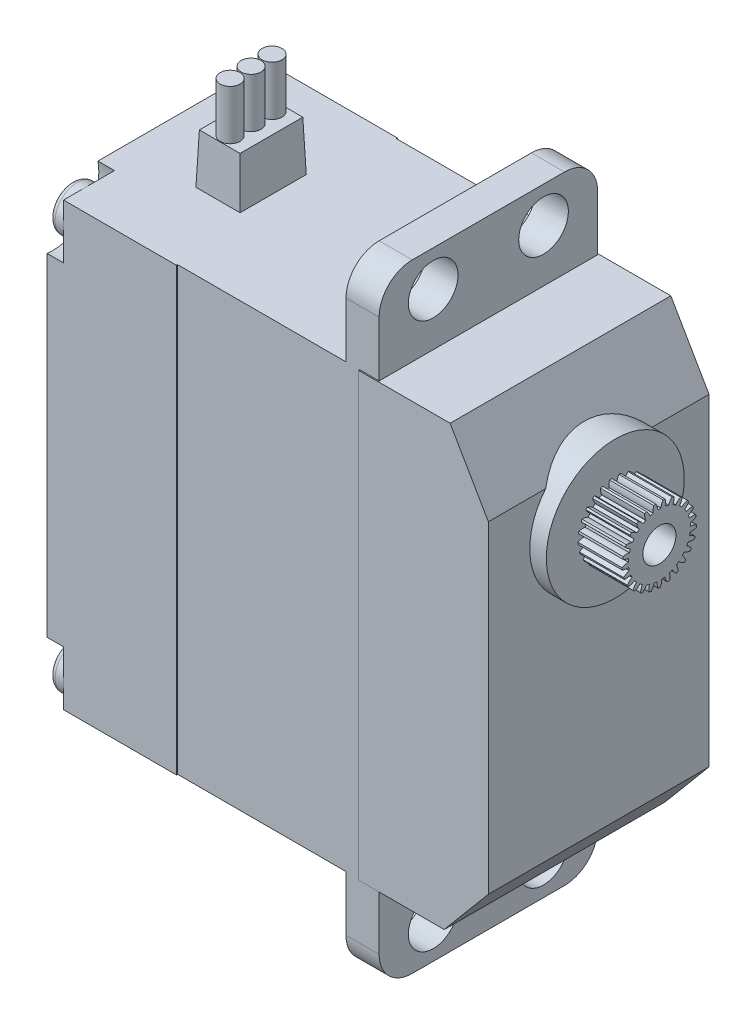
SolidWorks part; units mm, degrees
material "AISI 304"
ref_plane "前视基准面" through (0, 0, 0) normal (0, 0, 1) x (1, 0, 0)
ref_plane "上视基准面" through (0, 0, 0) normal (0, 1, 0) x (1, 0, 0)
ref_plane "右视基准面" through (0, 0, 0) normal (1, 0, 0) x (0, 0, -1)
sketch "草图1" plane through (0, 0, 0) normal (0, 0, 1) x (1, 0, 0)
  line L1 (-20, -20) -> (20, -20)
  line L2 (-20, -20) -> (-20, 20)
  line L3 (-20, 20) -> (20, 20)
  line L4 (20, -20) -> (20, 20)
  line L5 (-20, -20) -> (20, 20) construction
  line L6 (-20, 20) -> (20, -20) construction
  point P0 (0, 0)
  dimension "D1" = 40
  dimension "D2" = 40
extrude "凸台-拉伸1" add sketch "草图1" along normal blind 20
ref_plane "基准面1" through (20, 0, 0) normal (1, 0, 0) x (0, 0, -1)
sketch "草图2" plane through (20, 0, 0) normal (1, 0, 0) x (0, 0, -1)
  line L0 (-10, 20) -> (-10, 10) construction
  line L1 (-20, 20) -> (0, 20) construction
  line L2 (0, -20) -> (0, 20) construction
  line L3 (-20, -20) -> (-20, 20) construction
  circle A0 centre (-10, 10) radius 6.25
  dimension "D2" = 12.5
  dimension "D1" = 10
extrude "凸台-拉伸2" add sketch "草图2" along normal blind 1.5
ref_plane "基准面2" through (-20, 0, 0) normal (-1, 0, 0) x (0, 0, 1)
ref_plane "基准面5" through (20, 0, 0) normal (1, 0, 0) x (0, 0, -1)
ref_plane "基准面8" through (0, 0, 0) normal (0, 0, -1) x (-1, 0, 0)
sketch "草图10" plane through (0, 0, 0) normal (0, 0, -1) x (-1, 0, 0)
  line L0 (-20, 20) -> (20, 20) construction
  line L1 (-8.25, -20) -> (8.25, -20)
  line L2 (-8.25, -20) -> (-8.25, 20)
  line L3 (-8.25, 20) -> (8.25, 20)
  line L4 (8.25, -20) -> (8.25, 20)
  line L5 (-8.25, -20) -> (8.25, 20) construction
  line L6 (-8.25, 20) -> (8.25, -20) construction
  point P0 (0, 0)
  dimension "D1" = 16.5
extrude "切除-拉伸5" cut sketch "草图10" against normal blind 0.1
ref_plane "基准面9" through (0, 0, 20) normal (0, 0, 1) x (1, 0, 0)
sketch "草图11" plane through (0, 0, 20) normal (0, 0, 1) x (1, 0, 0)
  line L0 (20, 20) -> (-20, 20) construction
  line L1 (-8.25, -20) -> (8.25, -20)
  line L2 (-8.25, -20) -> (-8.25, 20)
  line L3 (-8.25, 20) -> (8.25, 20)
  line L4 (8.25, -20) -> (8.25, 20)
  line L5 (-8.25, -20) -> (8.25, 20) construction
  line L6 (-8.25, 20) -> (8.25, -20) construction
  point P0 (0, 0)
  dimension "D1" = 16.5
extrude "切除-拉伸6" cut sketch "草图11" against normal blind 0.1
ref_plane "基准面10" through (0, 20, 0) normal (0, 1, 0) x (1, 0, 0)
ref_plane "基准面11" through (0, -20, 0) normal (0, -1, 0) x (-1, 0, 0)
ref_plane "基准面12" through (21.5, 0, 0) normal (1, 0, 0) x (0, 0, -1)
sketch "草图14" plane through (21.5, 0, 0) normal (1, 0, 0) x (0, 0, -1)
  line L0 (-10, 20) -> (-10, -6.4918) construction
  line L1 (-20, 20) -> (0, 20) construction
  arc A0 (-8.8462, 13.116) -> (-9.1658, 12.6292) centre (-7.9898, 12.2054) ccw
  arc A1 (-9.1658, 12.6292) -> (-9.4375, 12.699) centre (-10, 9.9443) ccw
  arc A2 (-9.4375, 12.699) -> (-9.4831, 13.2795) centre (-10.6722, 12.8941) ccw
  arc A3 (-9.4831, 13.2795) -> (-9.6712, 13.3032) centre (-10, 9.9443) ccw
  arc A4 (-9.6712, 13.3032) -> (-9.8597, 12.7523) centre (-8.6153, 12.6343) ccw
  arc A5 (-9.8597, 12.7523) -> (-10.1403, 12.7523) centre (-10, 9.9443) ccw
  arc A6 (-10.1403, 12.7523) -> (-10.3288, 13.3032) centre (-11.3847, 12.6343) ccw
  arc A7 (-10.3288, 13.3032) -> (-10.5169, 13.2795) centre (-10, 9.9443) ccw
  arc A8 (-10.5169, 13.2795) -> (-10.5625, 12.699) centre (-9.3278, 12.8941) ccw
  arc A9 (-10.5625, 12.699) -> (-10.8342, 12.6292) centre (-10, 9.9443) ccw
  arc A10 (-10.8342, 12.6292) -> (-11.1538, 13.116) centre (-12.0102, 12.2054) ccw
  arc A11 (-11.1538, 13.116) -> (-11.3301, 13.0461) centre (-10, 9.9443) ccw
  arc A12 (-11.3301, 13.0461) -> (-11.2298, 12.4725) centre (-10.0825, 12.9686) ccw
  arc A13 (-11.2298, 12.4725) -> (-11.4757, 12.3374) centre (-10, 9.9443) ccw
  arc A14 (-11.4757, 12.3374) -> (-11.9063, 12.7294) centre (-12.5093, 11.6345) ccw
  arc A15 (-11.9063, 12.7294) -> (-12.0597, 12.6179) centre (-10, 9.9443) ccw
  arc A16 (-12.0597, 12.6179) -> (-11.82, 12.0873) centre (-10.832, 12.8531) ccw
  arc A17 (-11.82, 12.0873) -> (-12.0245, 11.8952) centre (-10, 9.9443) ccw
  arc A18 (-12.0245, 11.8952) -> (-12.539, 12.1678) centre (-12.8508, 10.9573) ccw
  arc A19 (-12.539, 12.1678) -> (-12.6599, 12.0217) centre (-10, 9.9443) ccw
  arc A20 (-12.6599, 12.0217) -> (-12.2957, 11.5673) centre (-11.5293, 12.5548) ccw
  arc A21 (-12.2957, 11.5673) -> (-12.446, 11.3305) centre (-10, 9.9443) ccw
  arc A22 (-12.446, 11.3305) -> (-13.0122, 11.4665) centre (-13.0132, 10.2165) ccw
  arc A23 (-13.0122, 11.4665) -> (-13.093, 11.2949) centre (-10, 9.9443) ccw
  arc A24 (-13.093, 11.2949) -> (-12.6272, 10.9454) centre (-12.1304, 12.0925) ccw
  arc A25 (-12.6272, 10.9454) -> (-12.7139, 10.6786) centre (-10, 9.9443) ccw
  arc A26 (-12.7139, 10.6786) -> (-13.2961, 10.6696) centre (-12.9862, 9.4586) ccw
  arc A27 (-13.2961, 10.6696) -> (-13.3317, 10.4833) centre (-10, 9.9443) ccw
  arc A28 (-13.3317, 10.4833) -> (-12.7937, 10.2606) centre (-12.5977, 11.4952) ccw
  arc A29 (-12.7937, 10.2606) -> (-12.8113, 9.9806) centre (-10, 9.9443) ccw
  arc A30 (-12.8113, 9.9806) -> (-13.373, 9.8271) centre (-12.7716, 8.7312) ccw
  arc A31 (-13.373, 9.8271) -> (-13.3611, 9.6378) centre (-10, 9.9443) ccw
  arc A32 (-13.3611, 9.6378) -> (-12.7845, 9.5559) centre (-12.9018, 10.8004) ccw
  arc A33 (-12.7845, 9.5559) -> (-12.732, 9.2803) centre (-10, 9.9443) ccw
  arc A34 (-12.732, 9.2803) -> (-13.2379, 8.992) centre (-12.3829, 8.0801) ccw
  arc A35 (-13.2379, 8.992) -> (-13.1792, 8.8116) centre (-10, 9.9443) ccw
  arc A36 (-13.1792, 8.8116) -> (-12.6005, 8.8756) centre (-13.0235, 10.0519) ccw
  arc A37 (-12.6005, 8.8756) -> (-12.481, 8.6218) centre (-10, 9.9443) ccw
  arc A38 (-12.481, 8.6218) -> (-12.8993, 8.2167) centre (-11.8444, 7.5461) ccw
  arc A39 (-12.8993, 8.2167) -> (-12.7977, 8.0565) centre (-10, 9.9443) ccw
  arc A40 (-12.7977, 8.0565) -> (-12.253, 8.2625) centre (-12.9553, 9.2965) ccw
  arc A41 (-12.253, 8.2625) -> (-12.0742, 8.0463) centre (-10, 9.9443) ccw
  arc A42 (-12.0742, 8.0463) -> (-12.3786, 7.5499) centre (-11.19, 7.1627) ccw
  arc A43 (-12.3786, 7.5499) -> (-12.2403, 7.4201) centre (-10, 9.9443) ccw
  arc A44 (-12.2403, 7.4201) -> (-11.764, 7.755) centre (-12.7014, 8.5819) ccw
  arc A45 (-11.764, 7.755) -> (-11.537, 7.5901) centre (-10, 9.9443) ccw
  arc A46 (-11.537, 7.5901) -> (-11.7084, 7.0336) centre (-10.4609, 6.9541) ccw
  arc A47 (-11.7084, 7.0336) -> (-11.5422, 6.9422) centre (-10, 9.9443) ccw
  arc A48 (-11.5422, 6.9422) -> (-11.1641, 7.3851) centre (-12.2777, 7.9529) ccw
  arc A49 (-11.1641, 7.3851) -> (-10.9033, 7.2818) centre (-10, 9.9443) ccw
  arc A50 (-10.9033, 7.2818) -> (-10.9308, 6.7002) centre (-9.7028, 6.9335) ccw
  arc A51 (-10.9308, 6.7002) -> (-10.7471, 6.653) centre (-10, 9.9443) ccw
  arc A52 (-10.7471, 6.653) -> (-10.4911, 7.176) centre (-11.7109, 7.4491) ccw
  arc A53 (-10.4911, 7.176) -> (-10.2128, 7.1409) centre (-10, 9.9443) ccw
  arc A54 (-10.2128, 7.1409) -> (-10.0948, 6.5706) centre (-8.9634, 7.102) ccw
  arc A55 (-10.0948, 6.5706) -> (-9.9052, 6.5706) centre (-10, 9.9443) ccw
  arc A56 (-9.9052, 6.5706) -> (-9.7872, 7.1409) centre (-11.0366, 7.102) ccw
  arc A57 (-9.7872, 7.1409) -> (-9.5089, 7.176) centre (-10, 9.9443) ccw
  arc A58 (-9.5089, 7.176) -> (-9.2529, 6.653) centre (-8.2891, 7.4491) ccw
  arc A59 (-9.2529, 6.653) -> (-9.0692, 6.7002) centre (-10, 9.9443) ccw
  arc A60 (-9.0692, 6.7002) -> (-9.0967, 7.2818) centre (-10.2972, 6.9335) ccw
  arc A61 (-9.0967, 7.2818) -> (-8.8359, 7.3851) centre (-10, 9.9443) ccw
  arc A62 (-8.8359, 7.3851) -> (-8.4578, 6.9422) centre (-7.7223, 7.9529) ccw
  arc A63 (-8.4578, 6.9422) -> (-8.2916, 7.0336) centre (-10, 9.9443) ccw
  arc A64 (-8.2916, 7.0336) -> (-8.463, 7.5901) centre (-9.5391, 6.9541) ccw
  arc A65 (-8.463, 7.5901) -> (-8.236, 7.755) centre (-10, 9.9443) ccw
  arc A66 (-8.236, 7.755) -> (-7.7597, 7.4201) centre (-7.2986, 8.5819) ccw
  arc A67 (-7.7597, 7.4201) -> (-7.6214, 7.5499) centre (-10, 9.9443) ccw
  arc A68 (-7.6214, 7.5499) -> (-7.9258, 8.0463) centre (-8.81, 7.1627) ccw
  arc A69 (-7.9258, 8.0463) -> (-7.747, 8.2625) centre (-10, 9.9443) ccw
  arc A70 (-7.747, 8.2625) -> (-7.2023, 8.0565) centre (-7.0447, 9.2965) ccw
  arc A71 (-7.2023, 8.0565) -> (-7.1007, 8.2167) centre (-10, 9.9443) ccw
  arc A72 (-7.1007, 8.2167) -> (-7.519, 8.6218) centre (-8.1556, 7.5461) ccw
  arc A73 (-7.519, 8.6218) -> (-7.3995, 8.8756) centre (-10, 9.9443) ccw
  arc A74 (-7.3995, 8.8756) -> (-6.8208, 8.8116) centre (-6.9765, 10.0519) ccw
  arc A75 (-6.8208, 8.8116) -> (-6.7621, 8.992) centre (-10, 9.9443) ccw
  arc A76 (-6.7621, 8.992) -> (-7.268, 9.2803) centre (-7.6171, 8.0801) ccw
  arc A77 (-7.268, 9.2803) -> (-7.2155, 9.5559) centre (-10, 9.9443) ccw
  arc A78 (-7.2155, 9.5559) -> (-6.6389, 9.6378) centre (-7.0982, 10.8004) ccw
  arc A79 (-6.6389, 9.6378) -> (-6.627, 9.8271) centre (-10, 9.9443) ccw
  arc A80 (-6.627, 9.8271) -> (-7.1887, 9.9806) centre (-7.2284, 8.7312) ccw
  arc A81 (-7.1887, 9.9806) -> (-7.2063, 10.2606) centre (-10, 9.9443) ccw
  arc A82 (-7.2063, 10.2606) -> (-6.6683, 10.4833) centre (-7.4023, 11.4952) ccw
  arc A83 (-6.6683, 10.4833) -> (-6.7039, 10.6696) centre (-10, 9.9443) ccw
  arc A84 (-6.7039, 10.6696) -> (-7.2861, 10.6786) centre (-7.0138, 9.4586) ccw
  arc A85 (-7.2861, 10.6786) -> (-7.3728, 10.9454) centre (-10, 9.9443) ccw
  arc A86 (-7.3728, 10.9454) -> (-6.907, 11.2949) centre (-7.8696, 12.0925) ccw
  arc A87 (-6.907, 11.2949) -> (-6.9878, 11.4665) centre (-10, 9.9443) ccw
  arc A88 (-6.9878, 11.4665) -> (-7.554, 11.3305) centre (-6.9868, 10.2165) ccw
  arc A89 (-7.554, 11.3305) -> (-7.7043, 11.5673) centre (-10, 9.9443) ccw
  arc A90 (-7.7043, 11.5673) -> (-7.3401, 12.0217) centre (-8.4707, 12.5548) ccw
  arc A91 (-7.3401, 12.0217) -> (-7.461, 12.1678) centre (-10, 9.9443) ccw
  arc A92 (-7.461, 12.1678) -> (-7.9755, 11.8952) centre (-7.1492, 10.9573) ccw
  arc A93 (-7.9755, 11.8952) -> (-8.18, 12.0873) centre (-10, 9.9443) ccw
  arc A94 (-8.18, 12.0873) -> (-7.9403, 12.6179) centre (-9.168, 12.8531) ccw
  arc A95 (-7.9403, 12.6179) -> (-8.0937, 12.7294) centre (-10, 9.9443) ccw
  arc A96 (-8.0937, 12.7294) -> (-8.5243, 12.3374) centre (-7.4907, 11.6345) ccw
  arc A97 (-8.5243, 12.3374) -> (-8.7702, 12.4725) centre (-10, 9.9443) ccw
  arc A98 (-8.7702, 12.4725) -> (-8.6699, 13.0461) centre (-9.9175, 12.9686) ccw
  arc A99 (-8.6699, 13.0461) -> (-8.8462, 13.116) centre (-10, 9.9443) ccw
extrude "凸台-拉伸6" add sketch "草图14" along normal blind 4
ref_plane "基准面13" through (25.5, 0, 0) normal (1, 0, 0) x (0, 0, -1)
sketch "草图15" plane through (25.5, 0, 0) normal (1, 0, 0) x (0, 0, -1)
  circle A0 centre (-10, 9.9443) radius 1.5
extrude "切除-拉伸9" cut sketch "草图15" against normal blind 4
ref_plane "基准面14" through (0, 20, 0) normal (0, 1, 0) x (1, 0, 0)
ref_plane "基准面15" through (-20, 0, 0) normal (-1, 0, 0) x (0, 0, 1)
chamfer "倒角2" distance 6 angle 30 1 edges at (20, 20, 10) first distance on face at (20, 0, 10)
chamfer "倒角3" distance 4 angle 50 1 edges at (20, -20, 10) first distance on face at (0, -20, 10)
ref_plane "基准面18" through (0, -20, 0) normal (0, -1, 0) x (-1, 0, 0)
sketch "草图20" plane through (0, -20, 0) normal (0, -1, 0) x (-1, 0, 0)
  line L0 (-20, 1.0461) -> (-20, -15.8444) construction
  line L2 (-20, 0) -> (-7, 0) construction
  line L3 (6.4625, 0) -> (-6.4625, 0) construction
  line L4 (-7, 0) -> (-7, -0.8546) construction
  line L7 (-5.9416, -19.9) -> (-4.5261, -19.9) construction
  line L9 (-6.0182, -0.1) -> (-4.3371, -0.1) construction
  line L10 (-7, -0.1) -> (-7, -19.9) construction
  line L11 (-7, -19.9) -> (-10, -19.9) construction
  line L12 (-10, -19.9) -> (-10, 0) construction
  line L13 (-10, 0) -> (-7, 0) construction
  line L14 (-10, -0.1) -> (-7, -0.1)
  line L15 (-7, -0.1) -> (-7, -19.9)
  line L16 (-7, -19.9) -> (-10, -19.9)
  line L17 (-10, -19.9) -> (-10, -0.1)
extrude "凸台-拉伸8" add sketch "草图20" along normal blind 8
sketch "草图21" plane through (0, 20, 0) normal (0, 1, 0) x (1, 0, 0)
  line L6 (7, -19.9) -> (10, -19.9)
  line L7 (7, -0.1) -> (7, -19.9)
  line L8 (10, -0.1) -> (7, -0.1)
  line L9 (10, -19.9) -> (10, -0.1)
  line L10 (7, -19.9) -> (10, -19.9)
  line L11 (7, -0.1) -> (7, -19.9)
  line L12 (10, -0.1) -> (7, -0.1)
  line L13 (10, -19.9) -> (10, -0.1)
  dimension "D1" = 0
extrude "凸台-拉伸9" add sketch "草图21" along normal blind 8
fillet "圆角4" radius 3 4 edges at (8.5, 28, 19.9) (8.5, 28, 0.1) (8.5, -28, 19.9) (8.5, -28, 0.1)
ref_plane "基准面19" through (10, 0, 0) normal (1, 0, 0) x (0, 0, -1)
sketch "草图22" plane through (10, 0, 0) normal (1, 0, 0) x (0, 0, -1)
  line L3 (-20.5235, 0) -> (-0.5503, 0) construction
  circle A0 centre (-15, 24.75) radius 2.25
  circle A1 centre (-5, 24.75) radius 2.25
  circle A2 centre (-5, -24.75) radius 2.25
  circle A3 centre (-15, -24.75) radius 2.25
  dimension "D1" = 49.5
  dimension "D2" = 49.5
extrude "切除-拉伸12" cut sketch "草图22" against normal blind 7.3
sketch "草图24" plane through (-20, 0, 0) normal (-1, 0, 0) x (0, 0, 1)
  line L0 (20, 0) -> (0, 0) construction
  line L1 (20, -6.4625) -> (20, 6.4625) construction
  line L2 (10, 0) -> (10, 28.881) construction
  line L3 (0, 6.4625) -> (0, -6.4625) construction
  line L4 (11, 20) -> (-11, 20) construction
  line L5 (0, 15.0598) -> (0, 20)
  line L6 (0, 20) -> (4.6197, 20)
  line L7 (20, 15.0598) -> (20, 20)
  line L8 (20, 20) -> (15.3803, 20)
  line L9 (0, -20) -> (4.6197, -20)
  line L10 (0, -15.0598) -> (0, -20)
  line L11 (20, -20) -> (15.3803, -20)
  line L12 (20, -15.0598) -> (20, -20)
  arc A1 (4.6197, 20) -> (0, 15.0598) centre (0.55, 19.1756) cw
  arc A2 (15.3803, 20) -> (20, 15.0598) centre (19.45, 19.1756) ccw
  arc A3 (4.6197, -20) -> (0, -15.0598) centre (0.55, -19.1756) ccw
  arc A5 (15.3803, -20) -> (20, -15.0598) centre (19.45, -19.1756) cw
extrude "切除-拉伸13" cut sketch "草图24" against normal blind 1.5
ref_plane "基准面20" through (-18.5, 0, 0) normal (-1, 0, 0) x (0, 0, 1)
sketch "草图25" plane through (-18.5, 0, 0) normal (-1, 0, 0) x (0, 0, 1)
  line L0 (0, 0) -> (20, 0) construction
  line L1 (20, -6.4625) -> (20, 6.4625) construction
  line L2 (10, 0) -> (10, 8.1993) construction
  circle A0 centre (2.0399, 17.9472) radius 2
  circle A1 centre (17.9601, 17.9472) radius 2
  circle A2 centre (2.0399, -17.9472) radius 2
  circle A3 centre (17.9601, -17.9472) radius 2
extrude "凸台-拉伸10" add sketch "草图25" along normal blind 1.3
fillet "圆角5" radius 0.5 4 edges at (-19.8, -17.9472, 19.9601) (-19.8, -17.9472, 0.0399) (-19.8, 17.9472, 15.9601) (-19.8, 17.9472, 4.0399)
ref_plane "基准面21" through (-19.8, 0, 0) normal (-1, 0, 0) x (0, 0, 1)
sketch "草图26" plane through (-19.8, 0, 0) normal (-1, 0, 0) x (0, 0, 1)
  line L0 (1.6399, 18.3472) -> (0.5942, 18.3472)
  line L1 (1.6399, 16.5015) -> (2.4399, 16.5015)
  line L2 (1.6399, 16.5015) -> (1.6399, 17.5472)
  line L3 (1.6399, 19.3929) -> (2.4399, 19.3929)
  line L4 (2.4399, 16.5015) -> (2.4399, 17.5472)
  line L5 (1.6399, 16.5015) -> (2.4399, 19.3929) construction
  line L6 (1.6399, 19.3929) -> (2.4399, 16.5015) construction
  line L7 (3.4855, 17.5472) -> (2.4399, 17.5472)
  line L8 (3.4855, 17.5472) -> (3.4855, 18.3472)
  line L9 (3.4855, 18.3472) -> (2.4399, 18.3472)
  line L10 (0.5942, 17.5472) -> (0.5942, 18.3472)
  line L11 (3.4855, 17.5472) -> (0.5942, 18.3472) construction
  line L12 (3.4855, 18.3472) -> (0.5942, 17.5472) construction
  line L13 (2.4399, 18.3472) -> (2.4399, 19.3929)
  line L14 (1.6399, 17.5472) -> (0.5942, 17.5472)
  line L15 (1.6399, 18.3472) -> (1.6399, 19.3929)
  line L16 (0, 0) -> (20.0276, 0) construction
  line L17 (10.0138, 0) -> (10.0138, 3.4562) construction
  line L18 (16.542, 18.3472) -> (19.4334, 17.5472) construction
  line L19 (16.542, 17.5472) -> (19.4334, 18.3472) construction
  line L20 (18.3877, 19.3929) -> (17.5877, 16.5015) construction
  line L21 (18.3877, 16.5015) -> (17.5877, 19.3929) construction
  line L22 (18.3877, 18.3472) -> (18.3877, 19.3929)
  line L23 (18.3877, 17.5472) -> (19.4334, 17.5472)
  line L24 (17.5877, 18.3472) -> (17.5877, 19.3929)
  line L25 (19.4334, 17.5472) -> (19.4334, 18.3472)
  line L26 (16.542, 18.3472) -> (17.5877, 18.3472)
  line L27 (16.542, 17.5472) -> (16.542, 18.3472)
  line L28 (16.542, 17.5472) -> (17.5877, 17.5472)
  line L29 (17.5877, 16.5015) -> (17.5877, 17.5472)
  line L30 (18.3877, 19.3929) -> (17.5877, 19.3929)
  line L31 (18.3877, 16.5015) -> (18.3877, 17.5472)
  line L32 (18.3877, 16.5015) -> (17.5877, 16.5015)
  line L33 (18.3877, 18.3472) -> (19.4334, 18.3472)
  line L34 (18.3877, -16.5015) -> (17.5877, -19.3929) construction
  line L35 (18.3877, -19.3929) -> (17.5877, -16.5015) construction
  line L36 (16.542, -17.5472) -> (19.4334, -18.3472) construction
  line L37 (16.542, -18.3472) -> (19.4334, -17.5472) construction
  line L38 (3.4855, -18.3472) -> (0.5942, -17.5472) construction
  line L39 (3.4855, -17.5472) -> (0.5942, -18.3472) construction
  line L40 (1.6399, -19.3929) -> (2.4399, -16.5015) construction
  line L41 (1.6399, -16.5015) -> (2.4399, -19.3929) construction
  line L42 (18.3877, -18.3472) -> (19.4334, -18.3472)
  line L43 (18.3877, -16.5015) -> (17.5877, -16.5015)
  line L44 (18.3877, -16.5015) -> (18.3877, -17.5472)
  line L45 (18.3877, -19.3929) -> (17.5877, -19.3929)
  line L46 (17.5877, -16.5015) -> (17.5877, -17.5472)
  line L47 (16.542, -17.5472) -> (17.5877, -17.5472)
  line L48 (16.542, -17.5472) -> (16.542, -18.3472)
  line L49 (16.542, -18.3472) -> (17.5877, -18.3472)
  line L50 (19.4334, -17.5472) -> (19.4334, -18.3472)
  line L51 (17.5877, -18.3472) -> (17.5877, -19.3929)
  line L52 (18.3877, -17.5472) -> (19.4334, -17.5472)
  line L53 (18.3877, -18.3472) -> (18.3877, -19.3929)
  line L54 (1.6399, -18.3472) -> (1.6399, -19.3929)
  line L55 (1.6399, -17.5472) -> (0.5942, -17.5472)
  line L56 (2.4399, -18.3472) -> (2.4399, -19.3929)
  line L57 (0.5942, -17.5472) -> (0.5942, -18.3472)
  line L58 (3.4855, -18.3472) -> (2.4399, -18.3472)
  line L59 (3.4855, -17.5472) -> (3.4855, -18.3472)
  line L60 (3.4855, -17.5472) -> (2.4399, -17.5472)
  line L61 (2.4399, -16.5015) -> (2.4399, -17.5472)
  line L62 (1.6399, -19.3929) -> (2.4399, -19.3929)
  line L63 (1.6399, -16.5015) -> (1.6399, -17.5472)
  line L64 (1.6399, -16.5015) -> (2.4399, -16.5015)
  line L65 (1.6399, -18.3472) -> (0.5942, -18.3472)
  circle A0 centre (2.0399, 17.9472) radius 1.5 construction
  point P0 (2.0399, 17.9472)
  point P8 (2.0399, 17.9472)
  point P34 (17.9877, 17.9472)
  point P59 (17.9877, -17.9472)
  point P60 (2.0399, -17.9472)
extrude "切除-拉伸14" cut sketch "草图26" against normal blind 0.8 draft 16
ref_plane "基准面22" through (0, 20, 0) normal (0, 1, 0) x (1, 0, 0)
sketch "草图28" plane through (0, 20, 0) normal (0, 1, 0) x (1, 0, 0)
  line L0 (-20, 0) -> (-20, -20) construction
  line L1 (-20, 11) -> (-20, -11) construction
  line L2 (-6.4625, -20) -> (6.4625, -20) construction
  line L3 (-20, -10) -> (-10.9126, -10) construction
  line L4 (-20, -10) -> (-9.5, -10) construction
  line L5 (-9.5, -10) -> (-9.5, -7)
  line L6 (-9.5, -7) -> (-13.5, -7)
  line L7 (-13.5, -7) -> (-13.5, -13)
  line L8 (-13.5, -13) -> (-9.5, -13)
  line L9 (-9.5, -13) -> (-9.5, -10)
extrude "凸台-拉伸11" add sketch "草图28" along normal blind 4.5 draft 2
ref_plane "基准面23" through (0, 24.5, 0) normal (0, 1, 0) x (1, 0, 0)
sketch "草图29" plane through (0, 24.5, 0) normal (0, 1, 0) x (1, 0, 0)
  line L0 (-11.5, -7.1571) -> (-11.5, -14.7571) construction
  line L1 (-9.6571, -7.1571) -> (-13.3429, -7.1571) construction
  line L2 (-11.5, -10.9571) -> (-11.5, -7.1571) construction
  line L3 (-11.5, -10.9571) -> (-11.5, -12.8429) construction
  line L4 (-13.3429, -12.8429) -> (-9.6571, -12.8429) construction
  circle A0 centre (-11.5, -11.9) radius 0.9
  circle A1 centre (-11.5, -8.1) radius 0.9
  circle A2 centre (-11.5, -10.0025) radius 0.9
extrude "凸台-拉伸12" add sketch "草图29" along normal blind 4.5
sketch "草图31" plane through (0, 0, 0.1) normal (0, 0, -1) x (-1, 0, 0)
  line L0 (-25.5, 13.3032) -> (-25.5, 6.57) construction
  line L1 (-25.5, 6.5706) -> (-25.5, 6.5693) construction
  line L2 (-25.5, 9.9366) -> (0, 9.9366) construction
  line L3 (0, 9.9366) -> (0, 0) construction
